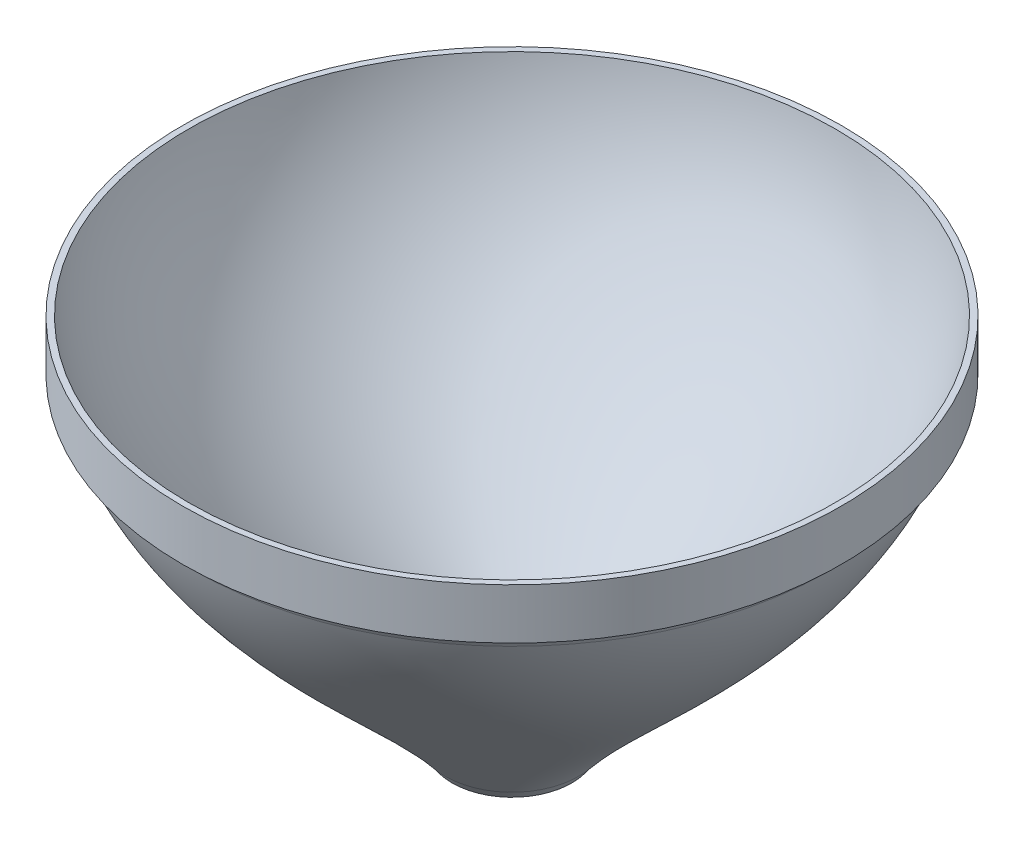
SolidWorks part; units mm, degrees
ref_plane "Płaszczyzna przednia" through (0, 0, 0) normal (0, 0, 1) x (1, 0, 0)
ref_plane "Płaszczyzna górna" through (0, 0, 0) normal (0, 1, 0) x (1, 0, 0)
ref_plane "Płaszczyzna prawa" through (0, 0, 0) normal (1, 0, 0) x (0, 0, -1)
sketch "Sketch1" plane through (0, 0, 0) normal (0, 0, 1) x (1, 0, 0)
  line L0 (-20.1658, 177.6565) -> (-20.1658, 45.3185)
  line L1 (-20.1658, 45.3185) -> (-18.1658, 45.3185)
  line L2 (-18.1658, 45.3185) -> (-18.1658, 175.6565)
  line L3 (-18.1658, 175.6565) -> (-4.1658, 175.6565)
  line L4 (-4.1658, 175.6565) -> (-4.1658, 174.0528)
  line L5 (-4.1658, 174.0528) -> (-2.6658, 174.0528)
  line L6 (-2.6658, 174.0528) -> (-2.6658, 175.6565)
  line L8 (24.8342, 176.1565) -> (24.8342, 177.6565)
  line L10 (-2.6658, 177.1565) -> (-2.6658, 182.6565)
  line L11 (-2.6658, 182.6565) -> (-4.1658, 182.6565)
  line L12 (-4.1658, 182.6565) -> (-4.1658, 177.6565)
  line L13 (-4.1658, 177.6565) -> (-20.1658, 177.6565)
  line L15 (24.8342, 148.4714) -> (24.8342, -40.5547) construction
  line L16 (-4.1658, 177.6565) -> (-4.1658, 175.6565)
  line L17 (-3.9845, 53.8719) -> (56.7742, 96.4156)
  line L21 (56.7742, 96.4156) -> (56.7742, 93.974)
  line L22 (56.7742, 93.974) -> (-3.4255, 51.8217)
  line L26 (18.8342, 85.6565) -> (16.872, 85.6565)
  line L30 (-18.1658, 128.7465) -> (-18.9658, 128.7465)
  line L32 (-18.1658, 135.4565) -> (-18.9658, 135.4565)
  line L33 (-18.9658, 135.4565) -> (-18.9658, 128.7465)
  line L34 (-18.1658, 128.5465) -> (-19.1658, 128.5465)
  line L35 (-19.1658, 128.5465) -> (-19.1658, 135.6565)
  line L36 (-19.1658, 135.6565) -> (-18.1658, 135.6565)
  line L37 (-2.6658, 177.1565) -> (-2.6658, 175.6565)
  line L38 (-17.5576, 127.3754) -> (-17.5576, 127.3754)
  line L39 (-17.5576, 127.3754) -> (-17.5576, 127.3754)
  line L40 (-17.5576, 127.3754) -> (-17.5576, 127.3754)
  line L41 (15.9828, 86.8645) -> (16.872, 85.6565)
  line L42 (-17.5576, 127.3754) -> (-18.1658, 128.7465)
  line L43 (15.9828, 86.8645) -> (15.9828, 86.8645) construction
  spline S0 degree 3 poles (-18.1658, 135.4565) (-14.4546, 112.7695) (7.6229, 100.7425) (18.8342, 85.6565) knots 0 0 0 0 1 1 1 1
  spline S1 degree 1 poles (-17.5576, 127.3754) (15.9828, 86.8645) knots 0 0 1 1 construction
  spline S2 degree 3 poles (-17.5576, 127.3754) (-17.1493, 126.2825) (-16.2379, 124.1197) (-14.13, 120.0244) (-9.7541, 113.3263) (-3.6348, 106.5855) (2.7798, 100.3454) (7.5389, 95.8197) (11.2889, 92.1067) (14.0705, 89.1159) (15.3533, 87.63) (15.9828, 86.8645) knots 0.117145 0.117145 0.117145 0.117145 0.169312 0.221479 0.325814 0.534482 0.638817 0.743151 0.847485 0.899652 0.95182 0.95182 0.95182 0.95182
  dimension "D1" = 2
  dimension "D3" = 2
  dimension "D4" = 5
  dimension "D5" = 1.5
  dimension "D6" = 45
  dimension "D2" = 0.2
  dimension "D10" = 0.2
  dimension "D11" = 0.2
  dimension "D7" = 6
  dimension "D12" = 7.11
  dimension "D8" = 1
  dimension "D13" = 40
  dimension "D14" = 90
  dimension "D9" = 1.5
revolve "Revolve1" add sketch "Sketch1" angle 360 about L15 region at (-18.5658, 132.1015, 0) region at (-17.5454, 132.1015, 0)
equation "\"outerdiameter\"= 45"
equation "\"D6@Sketch1\"=\"outerdiameter\""
equation "\"wallthick\"= 2"
equation "\"D1@Sketch1\"=\"wallthick\""
equation "\"D3@Sketch1\"=\"wallthick\""
